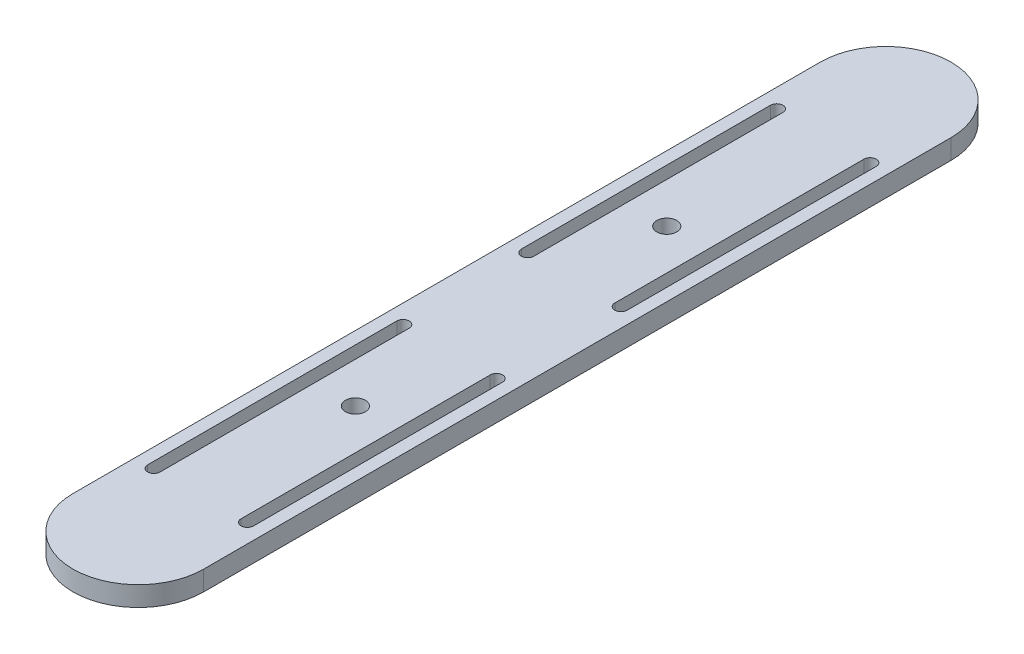
SolidWorks part; units mm, degrees
ref_plane "Front Plane" through (0, 0, 0) normal (0, 0, 1) x (1, 0, 0)
ref_plane "Top Plane" through (0, 0, 0) normal (0, 1, 0) x (1, 0, 0)
ref_plane "Right Plane" through (0, 0, 0) normal (1, 0, 0) x (0, 0, -1)
sketch "Sketch1" plane through (0, 0, 0) normal (0, 1, 0) x (1, 0, 0)
  line L0 (-10.5, 0) -> (-10.5, -120)
  line L1 (10.5, 0) -> (10.5, -120)
  arc A0 (10.5, 0) -> (-10.5, 0) centre (0, 0) ccw
  arc A1 (-10.5, -120) -> (10.5, -120) centre (0, -120) ccw
  dimension "D1" = 10.5
  dimension "D2" = 120
extrude "Boss-Extrude1" add sketch "Sketch1" along normal blind 3.175
sketch "Sketch2" plane through (0, 3.175, 0) normal (0, 1, 0) x (1, 0, 0)
  circle A0 centre (0, -35.15) radius 1.6 construction
  circle A1 centre (0, -85.15) radius 1.6 construction
  circle A2 centre (0, -35.15) radius 1.6
  circle A3 centre (0, -85.15) radius 1.6
extrude "Cut-Extrude1" cut sketch "Sketch2" against normal through all both and the other way through all
sketch "Sketch3" plane through (0, 0, 0) normal (0, -1, 0) x (1, 0, 0)
  line L0 (-8.5, 110) -> (-8.5, 70) construction
  line L1 (-6.5, 70) -> (-6.5, 110) construction
  line L2 (6.5, 110) -> (6.5, 70) construction
  line L3 (8.5, 70) -> (8.5, 110) construction
  line L4 (8.5, 10) -> (8.5, 50) construction
  line L5 (6.5, 50) -> (6.5, 10) construction
  line L6 (-8.5, 50) -> (-8.5, 10) construction
  line L7 (-6.5, 10) -> (-6.5, 50) construction
  line L8 (-8.5, 110) -> (-8.5, 70)
  line L9 (-6.5, 70) -> (-6.5, 110)
  line L10 (6.5, 110) -> (6.5, 70)
  line L11 (8.5, 70) -> (8.5, 110)
  line L12 (8.5, 10) -> (8.5, 50)
  line L13 (6.5, 50) -> (6.5, 10)
  line L14 (-8.5, 50) -> (-8.5, 10)
  line L15 (-6.5, 10) -> (-6.5, 50)
  arc A1 (-8.5, 70) -> (-6.5, 70) centre (-7.5, 70) ccw construction
  arc A2 (8.5, 110) -> (6.5, 110) centre (7.5, 110) ccw construction
  arc A3 (6.5, 70) -> (8.5, 70) centre (7.5, 70) ccw construction
  arc A4 (6.5, 10) -> (8.5, 10) centre (7.5, 10) ccw construction
  arc A5 (8.5, 50) -> (6.5, 50) centre (7.5, 50) ccw construction
  arc A6 (-6.5, 50) -> (-8.5, 50) centre (-7.5, 50) ccw construction
  arc A7 (-8.5, 10) -> (-6.5, 10) centre (-7.5, 10) ccw construction
  arc A8 (-8.5, 70) -> (-6.5, 70) centre (-7.5, 70) ccw
  arc A9 (8.5, 110) -> (6.5, 110) centre (7.5, 110) ccw
  arc A10 (6.5, 70) -> (8.5, 70) centre (7.5, 70) ccw
  arc A11 (6.5, 10) -> (8.5, 10) centre (7.5, 10) ccw
  arc A12 (8.5, 50) -> (6.5, 50) centre (7.5, 50) ccw
  arc A13 (-6.5, 50) -> (-8.5, 50) centre (-7.5, 50) ccw
  arc A14 (-8.5, 10) -> (-6.5, 10) centre (-7.5, 10) ccw
  arc A15 (-6.5, 110) -> (-8.5, 110) centre (-7.5, 110) ccw construction
  arc A16 (-6.5, 110) -> (-8.5, 110) centre (-7.5, 110) ccw
extrude "Cut-Extrude2" cut sketch "Sketch3" against normal through all both and the other way through all
